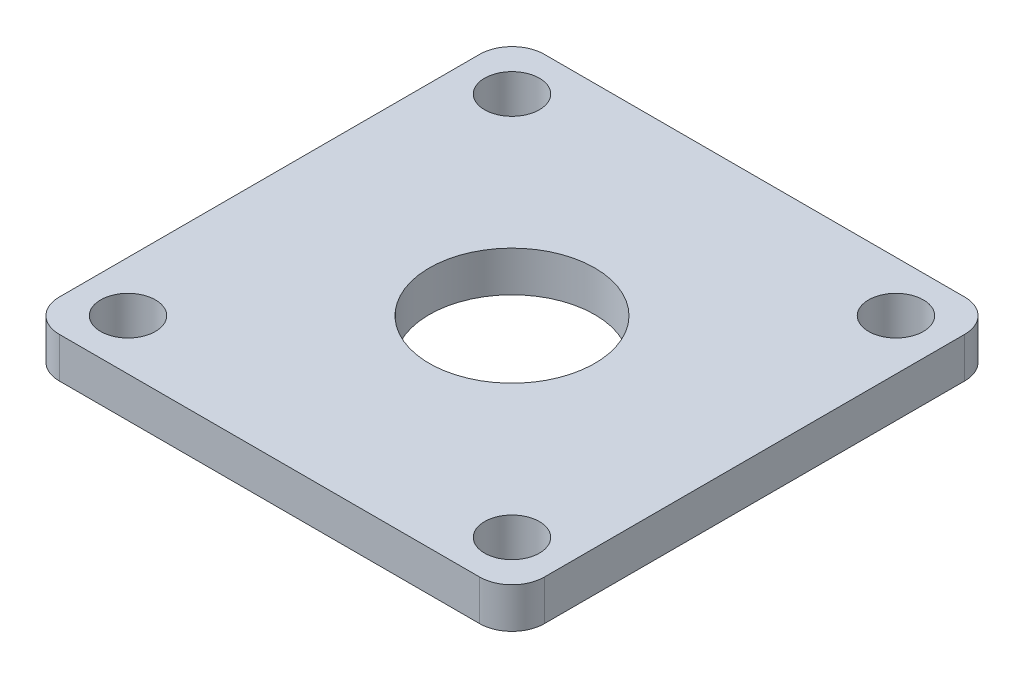
SolidWorks part; units mm, degrees
material "Alum Plate"
ref_plane "Front Plane" through (0, 0, 0) normal (0, 0, 1) x (1, 0, 0)
ref_plane "Top Plane" through (0, 0, 0) normal (0, 1, 0) x (1, 0, 0)
ref_plane "Right Plane" through (0, 0, 0) normal (1, 0, 0) x (0, 0, -1)
other "Bounding Box"
ref_plane "Default Plane" through (-8.9266, -12.7485, 0) normal (-0.1736, 0.9848, 0) x (0.9848, 0.1736, 0)
sketch "Sketch1" plane through (0, 0, 0) normal (0, 1, 0) x (1, 0, 0)
  line L0 (0, -12.5) -> (0, 12.5) construction
  line L1 (-14, 0) -> (0, 14) construction
  line L2 (-19.05, 19.05) -> (19.05, 19.05)
  line L3 (-19.05, 19.05) -> (-19.05, -19.05)
  line L4 (-19.05, -19.05) -> (19.05, -19.05)
  line L5 (19.05, 19.05) -> (19.05, -19.05)
  line L6 (-19.05, 19.05) -> (19.05, -19.05) construction
  line L7 (-19.05, -19.05) -> (19.05, 19.05) construction
  line L8 (8.8388, 8.8388) -> (-8.8388, 8.8388) construction
  line L9 (8.8388, 8.8388) -> (8.8388, -8.8388) construction
  line L10 (8.8388, -8.8388) -> (-8.8388, -8.8388) construction
  line L11 (-8.8388, 8.8388) -> (-8.8388, -8.8388) construction
  line L12 (8.8388, 8.8388) -> (-8.8388, -8.8388) construction
  line L13 (8.8388, -8.8388) -> (-8.8388, 8.8388) construction
  line L14 (-14, 0) -> (0, -14) construction
  line L15 (0, 14) -> (14, 0) construction
  line L16 (0, -14) -> (14, 0) construction
  line L17 (-14, 0) -> (14, 0) construction
  line L18 (0, 14) -> (0, -14) construction
  circle A0 centre (-15.24, 15.24) radius 1.3843 construction
  circle A1 centre (15.24, 15.24) radius 1.3843 construction
  circle A2 centre (15.24, -15.24) radius 1.3843 construction
  circle A3 centre (-15.24, -15.24) radius 1.3843 construction
  circle A4 centre (0, 0) radius 4
  circle A5 centre (8.8388, 8.8388) radius 1.5875
  circle A6 centre (8.8388, -8.8388) radius 1.5875
  circle A7 centre (-8.8388, -8.8388) radius 1.5875
  circle A8 centre (-8.8388, 8.8388) radius 1.5875
  circle A9 centre (-14, 0) radius 1.25
  circle A10 centre (0, 14) radius 1.25
  circle A11 centre (14, 0) radius 1.25
  circle A12 centre (0, -14) radius 1.25
  arc A13 (-9.8995, 9.8995) -> (0, 14) centre (0, 0) cw construction
  point P3 (0, 0)
  circle B0 centre (-9.8995, -9.8995) radius 1.2645 construction
  circle B1 centre (0, -8) radius 1.5875 construction
  circle B2 centre (0, 0) radius 4 construction
  circle B3 centre (9.8995, 9.8995) radius 1.2645 construction
  circle B4 centre (0, 8) radius 1.5875 construction
  circle B5 centre (9.8995, -9.8995) radius 1.2645 construction
  circle B6 centre (0, -12.5) radius 1.5875 construction
  circle B7 centre (-9.5, 0) radius 1.5875 construction
  circle B8 centre (-15.24, 15.24) radius 1.3843 construction
  circle B9 centre (15.24, 15.24) radius 1.3843 construction
  circle B10 centre (15.24, -15.24) radius 1.3843 construction
  circle B11 centre (-15.24, -15.24) radius 1.3843 construction
  circle B12 centre (9.5, 0) radius 1.5875 construction
  circle B13 centre (-9.8995, 9.8995) radius 1.2645 construction
  circle B14 centre (0, 12.5) radius 1.5875 construction
  dimension "D2" = 3.175
  dimension "D4" = 2.5
  dimension "D1" = 38.1
  dimension "D3" = 25
sketch_block_instance "Block-36mm gearbox motor block holes-1"
sketch_block "Block-36mm gearbox motor block holes"
extrude "Boss-Extrude1" add sketch "Sketch1" along normal mid plane 6.35 contours L5 L2 L3 L4 A12 A11 A9 A8 A10 A7 A6 A5 A4 A3 A2 A1 A0 region at (0, 0, -18.5112)
sketch "Sketch4" plane through (0, 0, 19.05) normal (0, 0, 1) x (1, 0, 0)
  line L0 (-5.5562, 0) -> (0, 0) construction
  line L1 (0, 0) -> (5.5562, 0) construction
  circle A0 centre (-5.5562, 0) radius 1.7272
  circle A1 centre (5.5562, 0) radius 1.7272
  dimension "D2" = 3.4544
  dimension "D1" = 11.1125
extrude "Cut-Extrude2" cut sketch "Sketch4" against normal blind 9.525
sketch "Sketch7" plane through (0, -3.175, 0) normal (0, -1, 0) x (1, 0, 0)
  line L0 (-19.05, 15.0813) -> (-15.0813, 15.0813) construction
  line L1 (-19.05, -19.05) -> (-19.05, 19.05) construction
  line L2 (-15.0813, 15.0813) -> (-15.0813, 19.05) construction
  line L3 (-19.05, 19.05) -> (19.05, 19.05) construction
  line L4 (0, 0) -> (-15.0813, 15.0813) construction
  line L5 (0, 0) -> (15.0813, 15.0812) construction
  circle A0 centre (-15.0813, 15.0813) radius 2.1526
  circle A1 centre (15.0813, 15.0812) radius 2.1527
  circle A2 centre (15.0812, -15.0813) radius 2.1527
  circle A3 centre (-15.0813, -15.0812) radius 2.1526
  dimension "D2" = 4.3053
  dimension "D1" = 3.9688
  dimension "D4" = 90
  dimension "D3" = 4
extrude "Cut-Extrude3" cut sketch "Sketch7" against normal through all
pattern_circular "CirPattern1" count 4 over 360 about axis through (0, 3.175, 0) along (0, -1, 0) of "Cut-Extrude2"
ref_plane "Plane1" through (0, -33.3502, 0) normal (0, -1, 0) x (-1, 0, 0)
sketch "Sketch6" plane through (0, -33.3502, 0) normal (0, -1, 0) x (-1, 0, 0)
  line L0 (19.05, 19.05) -> (-19.05, 19.05) construction
  line L1 (19.05, 19.05) -> (19.05, -19.05) construction
  line L2 (19.05, -19.05) -> (-19.05, -19.05) construction
  line L3 (-19.05, 19.05) -> (-19.05, -19.05) construction
  line L12 (19.05, 19.05) -> (-19.05, 19.05)
  line L13 (19.05, 19.05) -> (19.05, -19.05)
  line L14 (19.05, -19.05) -> (-19.05, -19.05)
  line L15 (-19.05, 19.05) -> (-19.05, -19.05)
  circle A8 centre (0, 0) radius 6.5
  circle A17 centre (-15.0812, 15.0813) radius 2.1526
  circle A18 centre (15.0813, 15.0812) radius 2.1526
  circle A19 centre (15.0813, -15.0813) radius 2.1527
  circle A20 centre (-15.0813, -15.0812) radius 2.1526
  circle A21 centre (-15.0812, 15.0813) radius 2.1527 construction
  dimension "D2" = 13
extrude "Boss-Extrude2" add sketch "Sketch6" along normal blind 3.175 separate body
fillet "Fillet1" radius 2.54 4 edges at (-19.05, 0, 19.05) (-19.05, 0, -19.05) (19.05, 0, -19.05) (19.05, 0, 19.05)
fillet "Fillet2" radius 2.54 4 edges at (-19.05, -34.9377, 19.05) (-19.05, -34.9377, -19.05) (19.05, -34.9377, -19.05) (19.05, -34.9377, 19.05)
delete or keep bodies "Body-Delete/Keep 1" type keep bodies bodies 108
delete or keep bodies "Body-Delete/Keep 2" [suppressed] type keep bodies bodies 107
